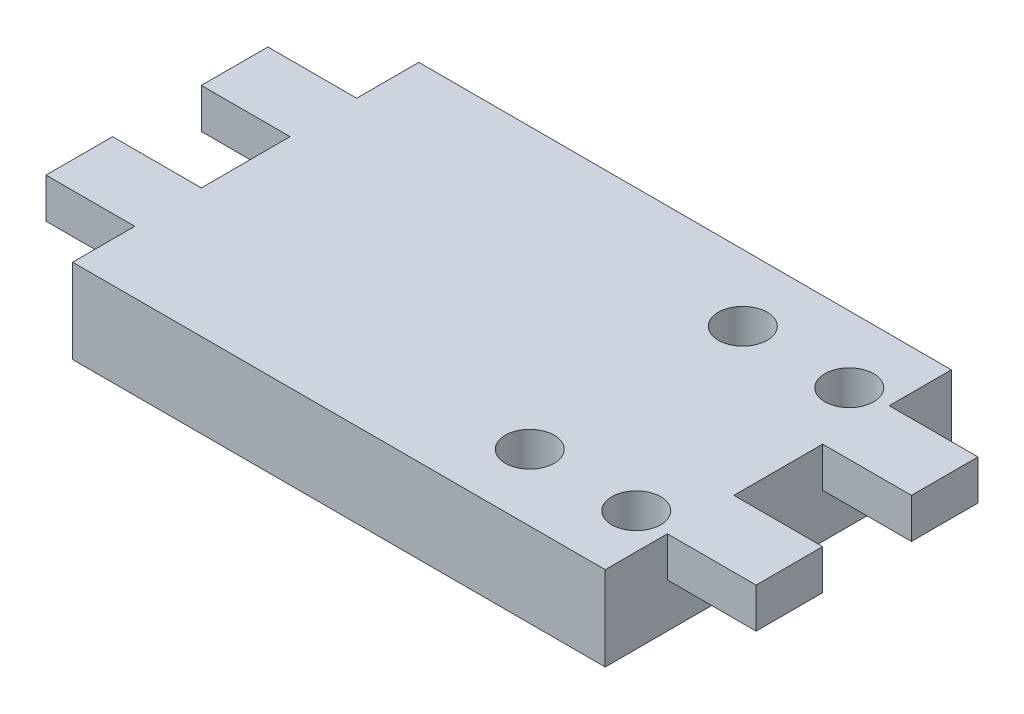
SolidWorks part; units mm, degrees
ref_plane "Front Plane" through (0, 0, 0) normal (0, 0, 1) x (1, 0, 0)
ref_plane "Top Plane" through (0, 0, 0) normal (0, 1, 0) x (1, 0, 0)
ref_plane "Right Plane" through (0, 0, 0) normal (1, 0, 0) x (0, 0, -1)
sketch "Sketch1" plane through (0, 0, 0) normal (1, 0, 0) x (0, 0, -1)
  line L1 (-12.5, -2.25) -> (12.5, -2.25)
  line L2 (-12.5, -2.25) -> (-12.5, 2.25)
  line L3 (-12.5, 2.25) -> (12.5, 2.25)
  line L4 (12.5, -2.25) -> (12.5, 2.25)
  line L5 (-12.5, -2.25) -> (12.5, 2.25) construction
  line L6 (-12.5, 2.25) -> (12.5, -2.25) construction
  point P0 (0, 0)
  dimension "D1" = 4.5
  dimension "D2" = 25
extrude "Boss-Extrude1" add sketch "Sketch1" along normal mid plane 60
sketch "Sketch2" plane through (30, 0, 0) normal (1, 0, 0) x (0, 0, -1)
  line L5 (12.5, 2.25) -> (-12.5, 2.25) construction
  line L6 (-12.5, 2.25) -> (-5, 2.25)
  line L7 (-12.5, 2.25) -> (-12.5, -2.25)
  line L8 (-12.5, -2.25) -> (-5, -2.25)
  line L9 (-5, 2.25) -> (-5, -2.25)
  line L10 (5, 2.25) -> (12.5, 2.25)
  line L11 (5, 2.25) -> (5, -2.25)
  line L12 (5, -2.25) -> (12.5, -2.25)
  line L13 (12.5, 2.25) -> (12.5, -2.25)
  line L14 (-12.5, -2.25) -> (12.5, -2.25) construction
  line L15 (-12.5, 2.25) -> (-12.5, -2.25) construction
  line L16 (12.5, -2.25) -> (12.5, 2.25) construction
  dimension "D1" = 7.5
  dimension "D2" = 7.5
extrude "Boss-Extrude2" add sketch "Sketch2" along normal blind 10
sketch "Esquisse1" plane through (0, 0, 12.5) normal (0, 0, 1) x (1, 0, 0)
  line L0 (40, -2.25) -> (-30, -2.25) construction
  line L1 (-30, 2.25) -> (30, 2.25)
  line L2 (-30, 2.25) -> (-30, -2.25)
  line L3 (-30, -2.25) -> (30, -2.25)
  line L4 (30, 2.25) -> (30, -2.25)
  dimension "D1" = 60
extrude "Boss.-Extru.1" add sketch "Esquisse1" along normal blind 7
mirror "Symétrie1" about plane through (0, 0, 0) normal (0, 0, 1) of "Boss.-Extru.1"
mirror "Mirror1" about plane through (0, 0, 0) normal (1, 0, 0) of "Boss-Extrude2"
sketch "Sketch6" plane through (0, -2.25, 0) normal (0, -1, 0) x (1, 0, 0)
  line L0 (-30, 19.5) -> (-30, -19.5)
  line L1 (-30, -19.5) -> (30, -19.5)
  line L2 (30, -19.5) -> (30, 19.5)
  line L3 (30, 19.5) -> (-30, 19.5)
extrude "Boss-Extrude3" add sketch "Sketch6" along normal blind 5
hole_wizard "CBORE for M3 SBHCS2" positions "Sketch4" profile "Sketch5" counterbore size "M3" standard "ANSI Metric" end condition through all
sketch "Sketch4" plane through (0, 2.25, 0) normal (0, -1, 0) x (-1, 0, 0)
  line L0 (-26, 12) -> (-26, -12) construction
  line L1 (-26, -12) -> (-14, -12) construction
  line L2 (-14, -12) -> (-14, 12) construction
  line L3 (-14, 12) -> (-26, 12) construction
  line L4 (-30, 19.5) -> (-30, -19.5) construction
  point P0 (-26, 12)
  point P3 (-14, 12)
  point P6 (-14, -12)
  point P9 (-26, -12)
  point P12 (-26, 12)
  point P13 (-26, -12)
  point P14 (-14, -12)
  point P15 (-14, 12)
  point P18 (-14, 0)
  dimension "D1" = 12
  dimension "D2" = 24
  dimension "D3" = 4
sketch "Sketch5" plane through (26, 2.25, -12) normal (1, 0, 0) x (0, 0, 1)
  line L0 (0, 0) -> (0, 9.5)
  line L1 (0, 9.5) -> (1.4, 9.5)
  line L3 (1.4, 9.5) -> (1.4, 8.1)
  line L4 (1.4, 8.1) -> (2.75, 8.1)
  line L5 (2.75, 8.1) -> (2.75, 0)
  line L7 (2.75, 0) -> (0, 0)
  line L11 (0, -6.35) -> (0, 107.95) construction
  dimension "Thru Hole Dia." = 2.8
  dimension "Thru Hole Depth" = 9.5
  dimension "C'Bore Dia." = 5.5
  dimension "C'Bore Depth" = 8.1
